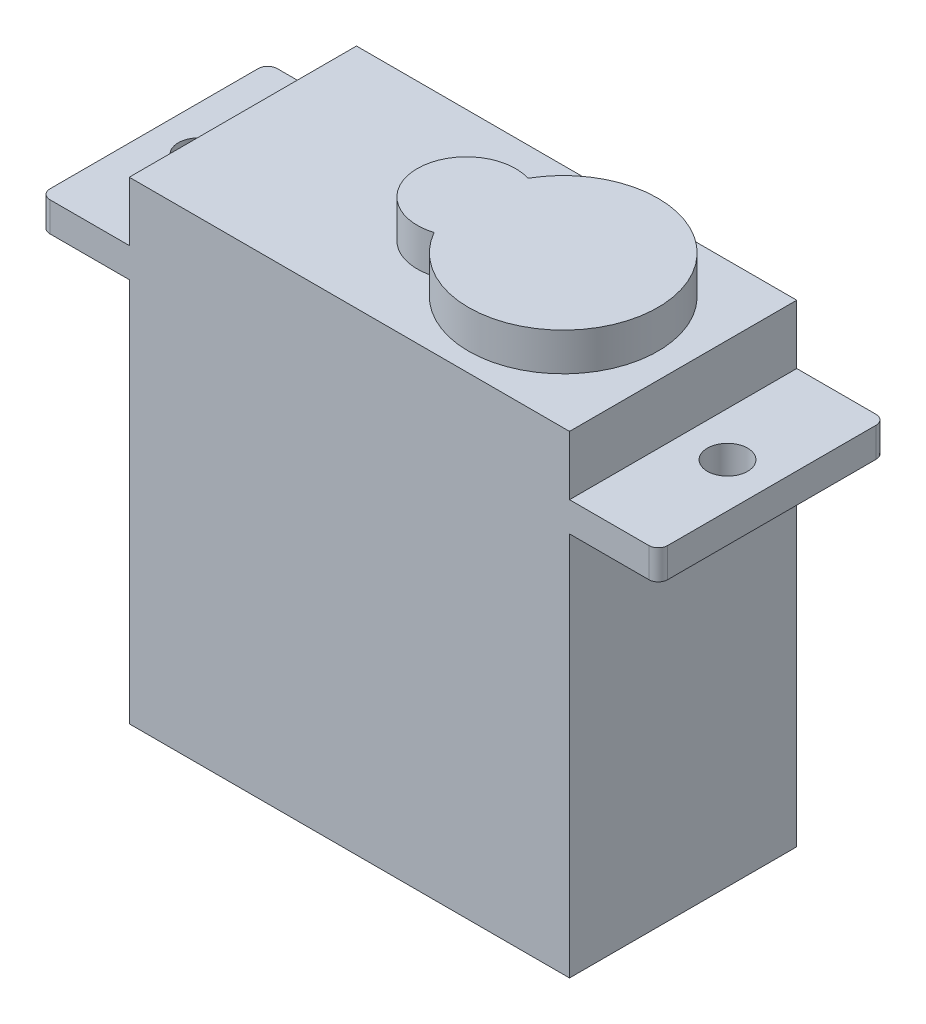
SolidWorks part; units mm, degrees
ref_plane "Front" through (0, 0, 0) normal (0, 0, 1) x (1, 0, 0)
ref_plane "Top" through (0, 0, 0) normal (0, 1, 0) x (1, 0, 0)
ref_plane "Right" through (0, 0, 0) normal (1, 0, 0) x (0, 0, -1)
sketch "Sketch1" plane through (0, 0, 0) normal (0, 1, 0) x (1, 0, 0)
  line L1 (-11.811, 6.096) -> (11.811, 6.096)
  line L2 (-11.811, 6.096) -> (-11.811, -6.096)
  line L3 (-11.811, -6.096) -> (11.811, -6.096)
  line L4 (11.811, 6.096) -> (11.811, -6.096)
  line L5 (-11.811, 6.096) -> (11.811, -6.096) construction
  line L6 (-11.811, -6.096) -> (11.811, 6.096) construction
  point P0 (0, 0)
  dimension "D1" = 12.192
  dimension "D2" = 23.622
extrude "Boss-Extrude1" add sketch "Sketch1" along normal blind 25.4
sketch "Sketch2" plane through (0, 25.4, 0) normal (0, 1, 0) x (1, 0, 0)
  line L0 (-55, 0) -> (55, 0) construction
  circle A0 centre (5.3787, 0) radius 5.0807
  arc A1 (0.9669, 2.5199) -> (0.9669, -2.5199) centre (0.1842, 0) ccw
extrude "Boss-Extrude2" add sketch "Sketch2" along normal blind 2.032 contours A0 | A0 A1 region at (5.3787, 25.4, 0) region at (-0.7459, 25.4, 0)
sketch "Sketch3" plane through (11.811, 0, 0) normal (1, 0, 0) x (0, 0, -1)
  line L0 (-6.096, 25.4) -> (-6.096, 0) construction
  line L1 (-6.096, 22.225) -> (6.096, 22.225)
  line L2 (-6.096, 22.225) -> (-6.096, 20.6375)
  line L3 (-6.096, 20.6375) -> (6.096, 20.6375)
  line L4 (6.096, 22.225) -> (6.096, 20.6375)
  line L5 (6.096, 25.4) -> (6.096, 0) construction
  line L6 (5.0807, 25.4) -> (-5.0807, 25.4) construction
  dimension "D1" = 3.175
  dimension "D2" = 1.5875
extrude "Boss-Extrude3" add sketch "Sketch3" along normal blind 4.7625
sketch "Sketch5" plane through (0, 22.225, 0) normal (0, 1, 0) x (1, 0, 0)
  line L0 (-15.0876, 0) -> (15.0876, 0) construction
  line L1 (16.5735, 6.096) -> (11.811, 6.096) construction
  circle A0 centre (14.1922, 0) radius 1.0795
  point P6 (14.1922, 6.096)
  dimension "D1" = 2.159
extrude "Cut-Extrude1" cut sketch "Sketch5" against normal up to next
mirror "Mirror1" about plane through (0, 0, 0) normal (1, 0, 0) of "Cut-Extrude1", "Boss-Extrude3"
fillet "Fillet1" radius 0.508 4 edges at (16.5735, 21.4312, 6.096) (16.5735, 21.4312, -6.096) (-16.5735, 21.4312, -6.096) (-16.5735, 21.4312, 6.096)
